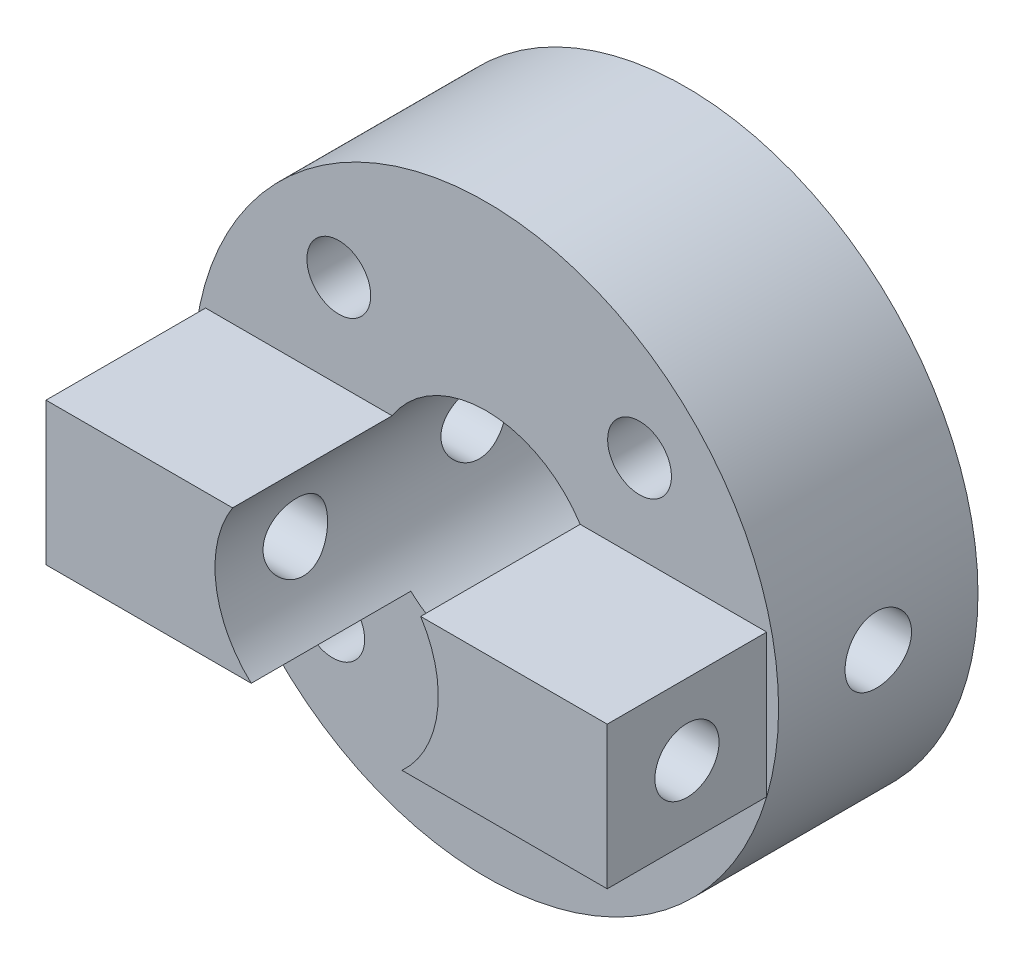
SolidWorks part; units mm, degrees
ref_plane "Front Plane" through (0, 0, 0) normal (0, 0, 1) x (1, 0, 0)
ref_plane "Top Plane" through (0, 0, 0) normal (0, 1, 0) x (1, 0, 0)
ref_plane "Right Plane" through (0, 0, 0) normal (1, 0, 0) x (0, 0, -1)
sketch "Sketch1" plane through (0, 0, 0) normal (0, 0, 1) x (1, 0, 0)
  circle A0 centre (-0.6551, 0.4169) radius 11
  circle A1 centre (-0.6551, 0.4169) radius 8 construction
  circle A2 centre (-0.6551, 0.4169) radius 8 construction
  circle A3 centre (-6.425, -5.1246) radius 1.2
  circle A6 centre (-0.6551, 0.4169) radius 4.2
extrude "Boss-Extrude1" add sketch "Sketch1" along normal blind 7.5 contours A0 | A6
sketch "Sketch2" plane through (0, 0, 0) normal (1, 0, 0) x (0, 0, -1)
  circle A0 centre (-3.75, 0.4169) radius 1.25
extrude "Cut-Extrude1" cut sketch "Sketch2" against normal through all and the other way through all
extrude "Cut-Extrude3" cut sketch "Sketch1<4>" along normal through all contours A3
sketch "Sketch1<4>" plane through (0, 0, 0) normal (0, 0, 1) x (1, 0, 0) same geometry as "Sketch1"
pattern_circular "CirPattern2" count 4 over 360 about axis through (-0.6551, 0.4169, 7.5) along (0, 0, 1) of "Cut-Extrude3"
sketch "Sketch3" plane through (0, 0, 7.5) normal (0, 0, 1) x (1, 0, 0)
  line L1 (-11.2096, 2.6821) -> (9.8993, 2.6821)
  line L2 (-11.2096, 2.6821) -> (-11.2096, -2.6821)
  line L3 (-11.2096, -2.6821) -> (9.8993, -2.6821)
  line L4 (9.8993, 2.6821) -> (9.8993, -2.6821)
  line L5 (-11.2096, 2.6821) -> (9.8993, -2.6821) construction
  line L6 (-11.2096, -2.6821) -> (9.8993, 2.6821) construction
  circle A0 centre (-0.6551, 0.4169) radius 11 construction
  point P0 (-0.6551, 0)
extrude "Boss-Extrude2" add sketch "Sketch3" along normal blind 6
sketch "Sketch4" plane through (-11.2096, 0, 0) normal (-1, 0, 0) x (0, 0, 1)
  circle A0 centre (10.5, 0) radius 1.2068
extrude "Cut-Extrude4" cut sketch "Sketch4" against normal through all
extrude "Cut-Extrude5" cut sketch "Sketch1<5>" along normal through all contours A6
sketch "Sketch1<5>" plane through (0, 0, 0) normal (0, 0, 1) x (1, 0, 0) same geometry as "Sketch1"
